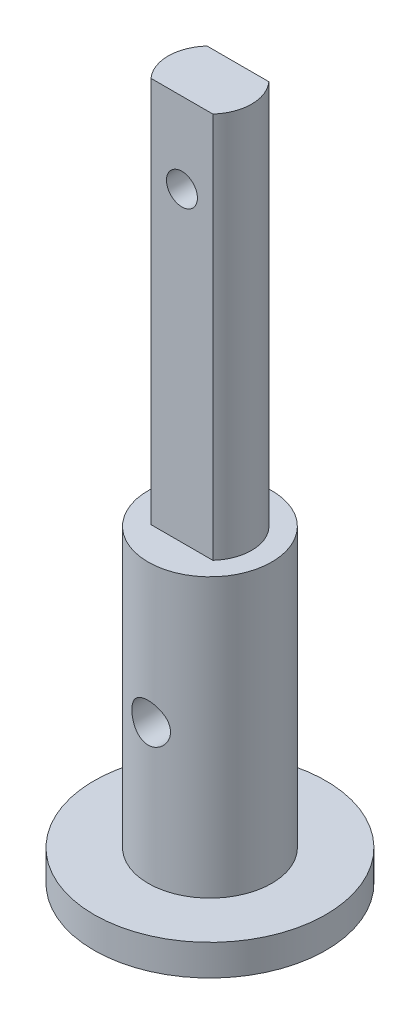
SolidWorks part; units mm, degrees
ref_plane "Front Plane" through (0, 0, 0) normal (0, 0, 1) x (1, 0, 0)
ref_plane "Top Plane" through (0, 0, 0) normal (0, 1, 0) x (1, 0, 0)
ref_plane "Right Plane" through (0, 0, 0) normal (1, 0, 0) x (0, 0, -1)
sketch "Sketch1" plane through (0, 0, 0) normal (0, 1, 0) x (1, 0, 0)
  circle A0 centre (0, 0) radius 7.5
  circle A1 centre (0, 0) radius 4
  dimension "D1" = 15
  dimension "D2" = 8
extrude "Boss-Extrude1" add sketch "Sketch1" along normal blind 2
extrude "Boss-Extrude2" add sketch "Sketch1<2>" along normal blind 45 contours A1 region at (0, 0, 0)
sketch "Sketch1<2>" plane through (0, 0, 0) normal (0, 1, 0) x (1, 0, 0) same geometry as "Sketch1"
sketch "Sketch2" plane through (0, 45, 0) normal (0, 1, 0) x (1, 0, 0)
  line L0 (-2, 1.8114) -> (2, 1.8114)
  line L1 (-3.8308, 0) -> (3.4281, 0) construction
  line L2 (-2, -1.8114) -> (2, -1.8114)
  arc A0 (-2, 1.8114) -> (-2, -1.8114) centre (0, 0) ccw
  arc A1 (2, -1.8114) -> (2, 1.8114) centre (0, 0) ccw
  circle A2 centre (0, 0) radius 4.5
extrude "Cut-Extrude1" cut sketch "Sketch2" against normal blind 25
sketch "Sketch3" plane through (0, 0, -1.8114) normal (0, 0, -1) x (-1, 0, 0)
  line L0 (0, 58.9249) -> (0, -1.0204) construction
  line L1 (4, 2) -> (-4, 2) construction
  circle A0 centre (0, 39.7943) radius 1
  circle A1 centre (0, 11) radius 1.25
  dimension "D1" = 9
extrude "Cut-Extrude2" cut sketch "Sketch3" against normal blind 25 and the other way blind 25 contours A1 L0 | L0 A1 | L0 A0 | A0 L0 region at (-0.4244, 39.7943, -1.8114) region at (-0.5305, 11, -1.8114) region at (0.5305, 11, -1.8114) region at (0.4244, 39.7943, -1.8114)
